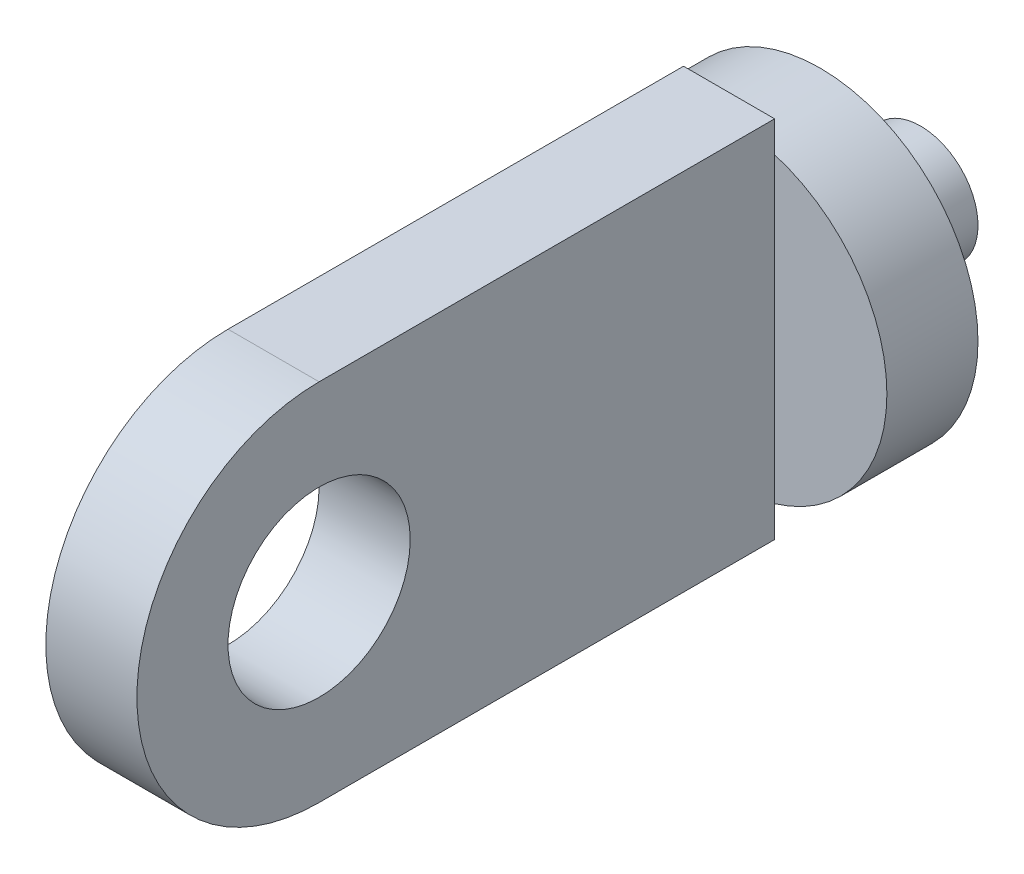
SolidWorks part; units mm, degrees
ref_plane "Front Plane" through (0, 0, 0) normal (0, 0, 1) x (1, 0, 0)
ref_plane "Top Plane" through (0, 0, 0) normal (0, 1, 0) x (1, 0, 0)
ref_plane "Right Plane" through (0, 0, 0) normal (1, 0, 0) x (0, 0, -1)
sketch "Sketch1" plane through (0, 0, 0) normal (1, 0, 0) x (0, 0, -1)
  circle A0 centre (0, 0) radius 12.7
  dimension "D1" = 25.4
extrude "Extrude-Thin1" add sketch "Sketch1" along normal blind 6.35 thin contours A0 thin type one direction reverse wall 6.35
ref_axis "Axis1" through (6.35, 0, 0) along (-1, 0, 0)
ref_plane "Plane1" through (3.175, 0, 0) normal (-1, 0, 0) x (0, 0, 1)
sketch "Sketch2" plane through (6.35, 0, 0) normal (1, 0, 0) x (0, 0, -1)
  line L0 (0, 12.7) -> (31.75, 12.7)
  line L1 (31.75, 12.7) -> (31.75, -12.7)
  line L2 (31.75, -12.7) -> (0, -12.7)
  circle A0 centre (0, 0) radius 12.7 construction
  arc A1 (0, -12.7) -> (0, 12.7) centre (0, 0) ccw
  dimension "D1" = 31.75
extrude "Boss-Extrude1" add sketch "Sketch2" against normal up to surface (6.35 mm away) up to face at (0, 0, -12.7)
sketch "Sketch3" plane through (0, 0, -31.75) normal (0, 0, -1) x (-1, 0, 0)
  line L0 (-3.175, -13.97) -> (-3.175, 13.97) construction
  line L1 (-6.35, 0) -> (0, 0) construction
  circle A0 centre (-3.175, 0) radius 11
  dimension "D1" = 22
extrude "Boss-Extrude2" add sketch "Sketch3" along normal blind 6.35
sketch "Sketch4" plane through (0, 0, -38.1) normal (0, 0, -1) x (-1, 0, 0)
  line L0 (-3.175, -13.97) -> (-3.175, 13.97) construction
  line L1 (-6.35, 0) -> (0, 0) construction
  circle A0 centre (-3.175, 0) radius 4
  circle A1 centre (-3.175, 0) radius 11 construction
  dimension "D1" = 8
extrude "Boss-Extrude3" add sketch "Sketch4" along normal blind 7
